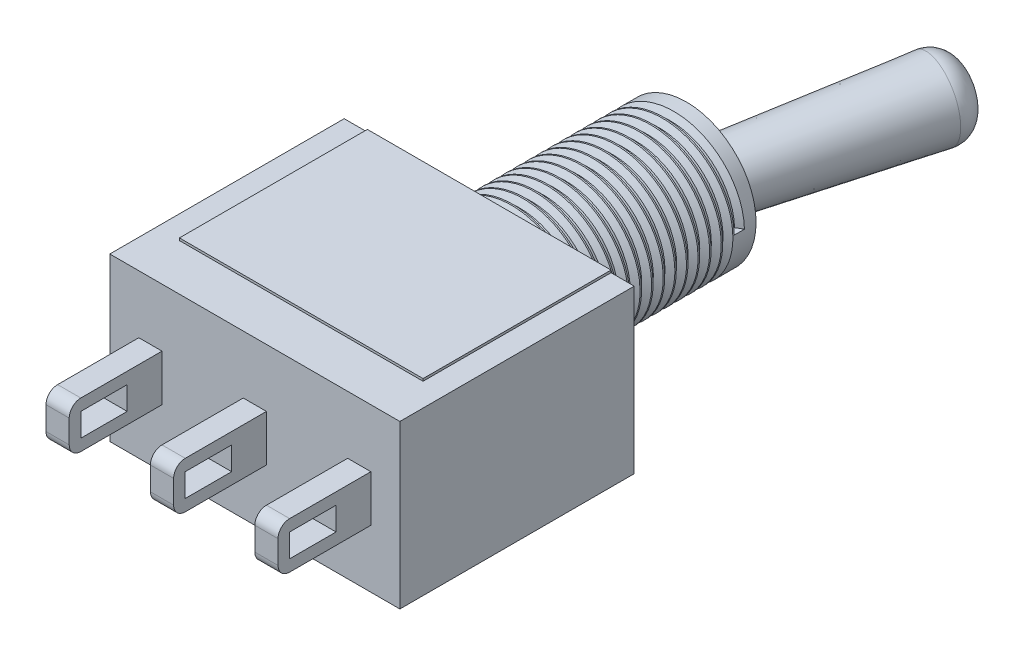
SolidWorks part; units mm, degrees
ref_plane "Front Plane" through (0, 0, 0) normal (0, 0, 1) x (1, 0, 0)
ref_plane "Top Plane" through (0, 0, 0) normal (0, 1, 0) x (1, 0, 0)
ref_plane "Right Plane" through (0, 0, 0) normal (1, 0, 0) x (0, 0, -1)
sketch "Sketch1" plane through (0, 0, 0) normal (0, 0, 1) x (1, 0, 0)
  line L1 (6.25, 3.5) -> (-6.25, 3.5)
  line L2 (6.25, 3.5) -> (6.25, -3.5)
  line L3 (6.25, -3.5) -> (-6.25, -3.5)
  line L4 (-6.25, 3.5) -> (-6.25, -3.5)
  line L5 (0, -3.5) -> (0, 3.5) construction
  line L6 (6.25, 0) -> (-6.25, 0) construction
  point P0 (0, 0)
  dimension "D1" = 12.5
  dimension "D2" = 7
extrude "Boss-Extrude1" add sketch "Sketch1" along normal blind 10
sketch "Sketch2" plane through (0, 0, 10) normal (0, 0, 1) x (1, 0, 0)
  line L0 (-5, 1) -> (-5, -1)
  line L1 (-5, 1) -> (-4, 1)
  line L2 (-5, -1) -> (-4, -1)
  line L3 (-4, 1) -> (-4, -1)
  line L4 (-0.5, 1) -> (-0.5, -1)
  line L5 (-0.5, 1) -> (0.5, 1)
  line L6 (-0.5, -1) -> (0.5, -1)
  line L7 (0.5, 1) -> (0.5, -1)
  line L8 (4, 1) -> (4, -1)
  line L9 (4, 1) -> (5, 1)
  line L10 (4, -1) -> (5, -1)
  line L11 (5, 1) -> (5, -1)
  point P0 (0, 1)
  point P11 (-0.5, 0)
  point P14 (4.5, 1)
  point P16 (-4.5, 1)
  dimension "D1" = 1
  dimension "D2" = 2
  dimension "D3" = 4.5
  dimension "D4" = 4.5
extrude "Boss-Extrude2" add sketch "Sketch2" along normal blind 4
sketch "Sketch3" plane through (-5, 0, 0) normal (-1, 0, 0) x (0, 0, 1)
  line L0 (14, 1) -> (14, -1) construction
  line L1 (13.5, 0.5) -> (11.5, 0.5)
  line L2 (13.5, 0.5) -> (13.5, -0.5)
  line L3 (13.5, -0.5) -> (11.5, -0.5)
  line L4 (11.5, 0.5) -> (11.5, -0.5)
  line L5 (12.5, -0.5) -> (12.5, 0.5) construction
  line L6 (13.5, 0) -> (11.5, 0) construction
  point P0 (12.5, 0)
  dimension "D1" = 0.5
  dimension "D2" = 2
  dimension "D3" = 1
extrude "Cut-Extrude1" cut sketch "Sketch3" against normal through all
sketch "Sketch14" plane through (0, 0, 0) normal (0, 0, -1) x (-1, 0, 0)
  line L0 (-6.25, -3.5) -> (6.25, -3.5)
  line L1 (-6.25, -3.5) -> (-6.25, 3.5)
  line L2 (6.25, -3.5) -> (6.25, 3.5)
  line L3 (-6.25, 3.5) -> (6.25, 3.5)
  line L4 (-6.25, 3.5) -> (6.25, 3.5) construction
extrude "Boss-Extrude9" add sketch "Sketch14" along normal blind 0.1
sketch "Sketch15" plane through (0, 3.5, 0) normal (0, 1, 0) x (1, 0, 0)
  line L0 (-5.25, 0.1) -> (-5.25, -8)
  line L1 (-5.25, 0.1) -> (5.25, 0.1)
  line L2 (-5.25, -8) -> (5.25, -8)
  line L3 (5.25, 0.1) -> (5.25, -8)
  line L4 (-6.25, 0.1) -> (6.25, 0.1) construction
  line L5 (-6.25, -10) -> (-6.25, 0.1) construction
  line L6 (6.25, -10) -> (6.25, 0.1) construction
  line L7 (6.25, -10) -> (-6.25, -10) construction
  dimension "D1" = 1
  dimension "D2" = 1
  dimension "D3" = 2
extrude "Boss-Extrude10" add sketch "Sketch15" along normal blind 0.1
sketch "Sketch16" plane through (0, -3.5, 0) normal (0, -1, 0) x (-1, 0, 0)
  line L0 (-5.25, 0.1) -> (-5.25, -8)
  line L1 (-5.25, 0.1) -> (5.25, 0.1)
  line L2 (-5.25, -8) -> (5.25, -8)
  line L3 (5.25, 0.1) -> (5.25, -8)
  line L4 (-6.25, 0.1) -> (6.25, 0.1) construction
  line L5 (6.25, -10) -> (-6.25, -10) construction
  line L6 (-6.25, -10) -> (-6.25, 0.1) construction
  line L7 (6.25, -10) -> (6.25, 0.1) construction
  dimension "D1" = 2
  dimension "D2" = 1
  dimension "D3" = 1
extrude "Boss-Extrude11" add sketch "Sketch16" along normal blind 0.1
fillet "Fillet1" radius 0.5 6 edges at (4.5, 1, 14) (4.5, -1, 14) (0, 1, 14) (0, -1, 14) (-4.5, 1, 14) (-4.5, -1, 14)
sketch "Sketch4" plane through (0, 0, -0.1) normal (0, 0, -1) x (-1, 0, 0)
  circle A0 centre (0, 0) radius 3
  dimension "D1" = 6
extrude "Boss-Extrude3" add sketch "Sketch4" along normal blind 8.5
sketch "Sketch5" plane through (0, 0, -8.6) normal (0, 0, -1) x (-1, 0, 0)
  circle A0 centre (0, 0) radius 2.5
  circle A1 centre (0, 0) radius 3 construction
  dimension "D1" = 0.5
extrude "Cut-Extrude2" cut sketch "Sketch5" against normal blind 1.5
thread "Thread1" pitch 0.5 method cut profile "Thread Profile1" start angle 0, offset 0.5, length 10, pitch 0.5, diameter 6
ref_plane "Plane1" through (3, 0, -8.1) normal (0, -1, 0) x (1, 0, 0)
sketch "Thread Profile1" plane through (3, 0, -8.1) normal (0, -1, 0) x (1, 0, 0)
  line L0 (0, 0) -> (0, 0.5) construction
  line L11 (0, 0) -> (0, 0.4375)
  line L12 (0, 0.4375) -> (-0.2706, 0.2812)
  line L13 (-0.2706, 0.2812) -> (-0.2706, 0.1562)
  line L15 (-0.2706, 0.1562) -> (0, 0)
  line L17 (-0.2706, 0.2187) -> (0, 0.2187) construction
  point P2 (0, 0)
  dimension "Pitch" = 0.5
  dimension "Profile_Angle" = 60
  dimension "Profile_Land" = 0.125
  dimension "Profile_Height" = 0.2706
sketch "Sketch9" plane through (0, 0, -7.1) normal (0, 0, -1) x (-1, 0, 0)
  line L0 (0, 0) -> (-0.2929, -2.246) construction
ref_plane "Plane3" through (1.7601, 0.2295, -6.6244) normal (0.2566, 0.0335, -0.9659) x (0.1293, -0.9916, 0)
sketch "Sketch10" plane through (1.7601, 0.2295, -6.6244) normal (0.2566, 0.0335, -0.9659) x (0.1293, -0.9916, 0)
  circle A0 centre (0, 1.8376) radius 1.25
  dimension "D1" = 2.5
extrude "Boss-Extrude5" add sketch "Sketch10" along normal blind 11 draft 2 draft outward yes
fillet "Fillet2" radius 1 1 edges at (1.2438, 0.3682, -18.1448)
